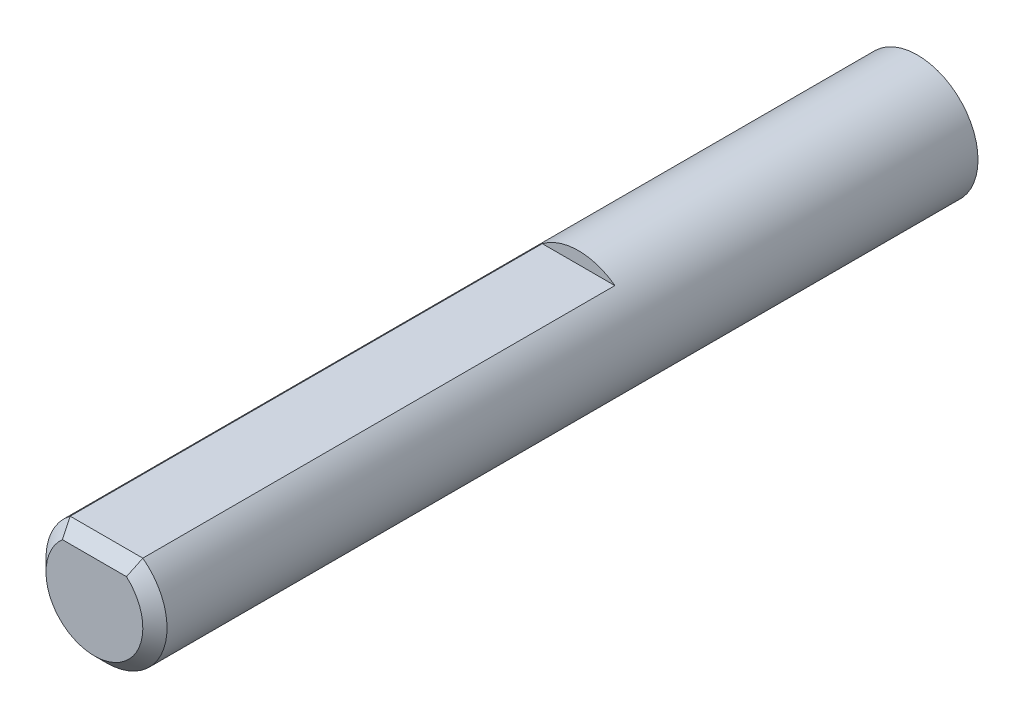
SolidWorks part; units mm, degrees
ref_plane "前视基准面" through (0, 0, 0) normal (0, 0, 1) x (1, 0, 0)
ref_plane "上视基准面" through (0, 0, 0) normal (0, 1, 0) x (1, 0, 0)
ref_plane "右视基准面" through (0, 0, 0) normal (1, 0, 0) x (0, 0, -1)
sketch "草图1" plane through (0, 0, 0) normal (0, 0, 1) x (1, 0, 0)
  line L0 (0, -21.15) -> (0, 21.15) construction
  line L1 (18.3216, 21.15) -> (-18.3216, 21.15)
  line L2 (-18.3216, 21.15) -> (-21.15, 18.3216)
  line L3 (-21.15, 18.3216) -> (-21.15, -18.3216)
  line L4 (-21.15, -18.3216) -> (-18.3216, -21.15)
  line L5 (-18.3216, -21.15) -> (18.3216, -21.15)
  line L6 (21.15, -18.3216) -> (18.3216, -21.15)
  line L7 (18.3216, 21.15) -> (21.15, 18.3216)
  line L8 (21.15, 18.3216) -> (21.15, -18.3216)
  line L9 (-19.7358, 19.7358) -> (0, 0) construction
  line L10 (-15.5, 15.5) -> (15.5, 15.5) construction
  circle A4 centre (0, 0) radius 15.5
  circle A6 centre (0, 0) radius 11
  circle A8 centre (0, 0) radius 2.5
  dimension "D8" = 5
  dimension "D9" = 22
  dimension "D1" = 135
  dimension "D2" = 42.3
  dimension "D3" = 42.3
  dimension "D4" = 4
  dimension "D6" = 31
extrude "凸台-拉伸5" add sketch "草图1" along normal blind 34 separate body contours A8 region at (0, 0, 0)
sketch "草图4" plane through (0, 0, 34) normal (0, 0, 1) x (1, 0, 0)
  line L0 (-1.5, 2) -> (1.5, 2)
  circle A1 centre (0, 0) radius 2.5
  arc A2 (1.5, 2) -> (-1.5, 2) centre (0, 0) ccw
  dimension "D2" = 0.5
  dimension "D1" = 0
extrude "切除-拉伸2" cut sketch "草图4" against normal blind 20
chamfer "倒角2" distance 0.5 2 edges at (0, 2, 34) (0, -2.5, 34)
